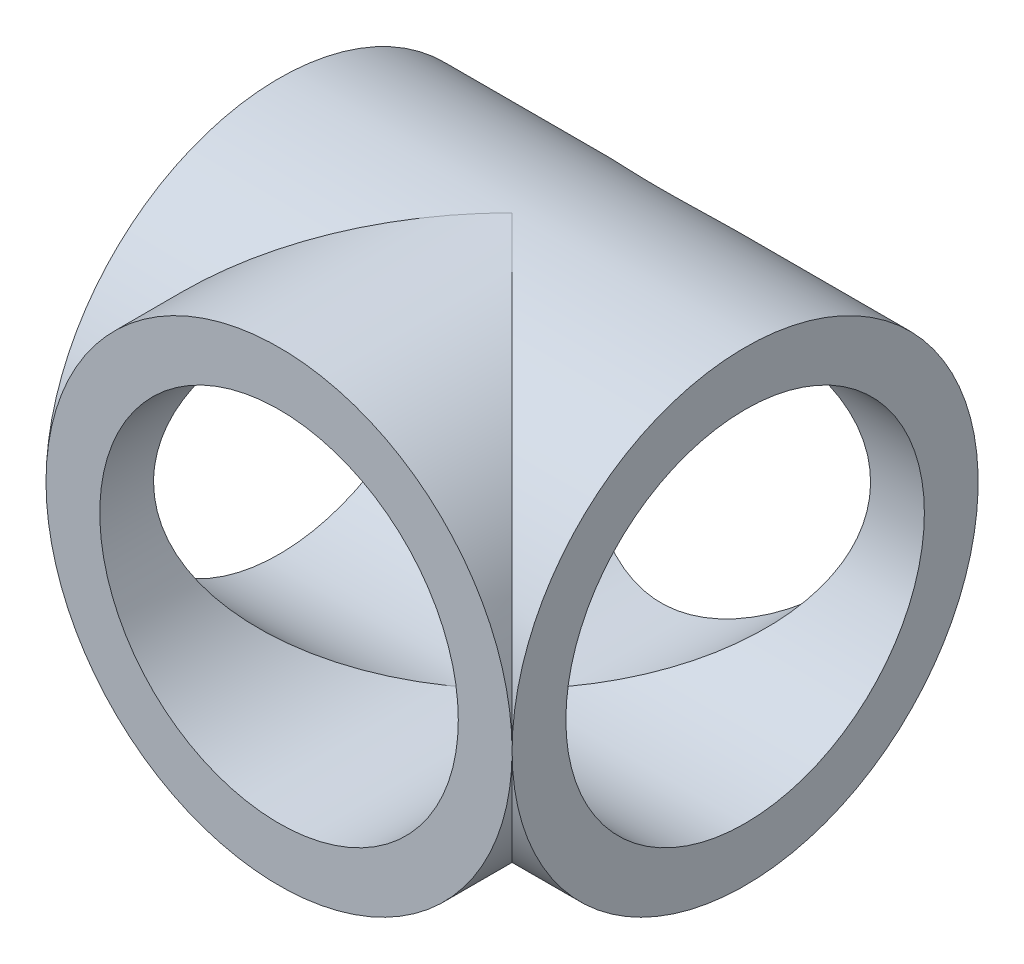
SolidWorks part; units mm, degrees
ref_plane "Front Plane" through (0, 0, 0) normal (0, 0, 1) x (1, 0, 0)
ref_plane "Top Plane" through (0, 0, 0) normal (0, 1, 0) x (1, 0, 0)
ref_plane "Right Plane" through (0, 0, 0) normal (1, 0, 0) x (0, 0, -1)
sketch "Sketch46" plane through (0, 0, 0) normal (1, 0, 0) x (0, 0, -1)
  circle A0 centre (0, 0) radius 13
  dimension "D1" = 26
extrude "Boss-Extrude4" add sketch "Sketch46" along normal blind 13 and the other way blind 13
sketch "Sketch47" plane through (0, 0, 0) normal (0, 0, 1) x (1, 0, 0)
  circle A0 centre (0, 0) radius 13
  dimension "D1" = 26
extrude "Boss-Extrude5" add sketch "Sketch47" along normal blind 13
sketch "Sketch48" plane through (0, 0, 13) normal (0, 0, 1) x (1, 0, 0)
  circle A0 centre (0, 0) radius 10
  dimension "D1" = 20
extrude "Cut-Extrude1" cut sketch "Sketch48" against normal blind 33
sketch "Sketch49" plane through (-13, 0, 0) normal (-1, 0, 0) x (0, 0, 1)
  circle A0 centre (0, 0) radius 10
  dimension "D1" = 20
extrude "Cut-Extrude2" cut sketch "Sketch49" against normal blind 33
